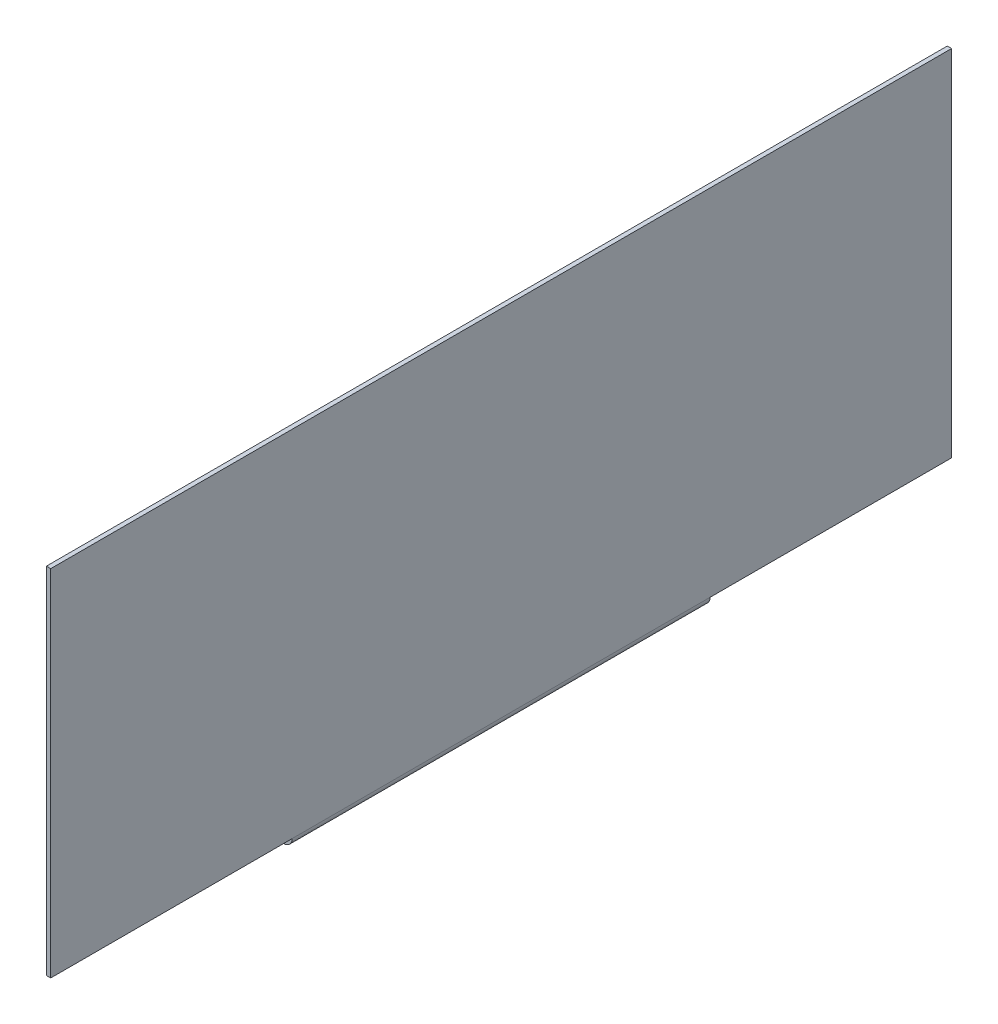
SolidWorks part; units mm, degrees
note: The reader was unsure of these and kept them because the rebuilt part matched: flange length of "Edge-Flange1".
material "6061-T6 (SS)"
ref_plane "X-Y Datum" through (0, 0, 0) normal (0, 0, 1) x (1, 0, 0)
ref_plane "X-Z Datum" through (0, 0, 0) normal (0, 1, 0) x (1, 0, 0)
ref_plane "Y-Z Datum" through (0, 0, 0) normal (1, 0, 0) x (0, 0, -1)
sketch "Sketch1" plane through (0, 0, 0) normal (1, 0, 0) x (0, 0, -1)
  line L1 (-330.7931, 130.175) -> (330.7931, 130.175)
  line L2 (-330.7931, 130.175) -> (-330.7931, -130.175)
  line L3 (-330.7931, -130.175) -> (330.7931, -130.175)
  line L4 (330.7931, 130.175) -> (330.7931, -130.175)
  line L5 (-330.7931, 130.175) -> (330.7931, -130.175) construction
  line L6 (-330.7931, -130.175) -> (330.7931, 130.175) construction
  point P0 (0, 0)
  dimension "D1" = 661.5862
  dimension "D2" = 260.35
base flange "Base-Flange1" sketch "Sketch1" thickness 3.175 reverse thickness direction no parameters "D1"=1
edge flange "Edge-Flange1" sketch "Sketch4" flange angle 90 flange length 25.4 flange position bend outside bend radius 3.175 thickness 3.175 relief rectangular parameters "D6"=10
sketch "Sketch4" plane through (-3.175, -130.175, 0) normal (0, 1, 0) x (0, 0, -1)
  line L3 (-153.4389, 22.225) -> (153.4389, 22.225)
  line L5 (330.7931, 0) -> (-330.7931, 0) construction
  line L6 (153.4389, 0) -> (-153.4389, 0)
  line L8 (-153.4389, 22.225) -> (-153.4389, 0)
  line L10 (153.4389, 22.225) -> (153.4389, 0)
bend "EdgeBend1" bend radius 3.175 bend angle 90 parameters "D5"=1
sketch "Bend-Lines1" [suppressed] plane through (0, 0, 0) normal (0, 1, 0) x (1, 0, 0)
sketch "Bounding-Box1" [suppressed] plane through (0, 0, 0) normal (0, 1, 0) x (1, 0, 0)
sheet metal parameters "Sheet-Metal1" thickness 3.175 parameters "D1"=1
flat pattern "Flat-Pattern1" [suppressed]
sketch "Bend-Lines2" plane through (0, 0, 0) normal (0, 1, 0) x (1, 0, 0)
sketch3d "Bounding-Box2" [suppressed]
  line L0 (-312.7426, -107.4737, 0) -> (312.7426, -107.4737, 0) construction
  line L1 (-312.7426, 107.4738, 0) -> (312.7426, 107.4738, 0) construction
  line L2 (-312.7426, -107.4737, 0) -> (-312.7426, 107.4738, 0) construction
  line L3 (312.7426, -107.4737, 0) -> (312.7426, 107.4738, 0) construction
sheet metal parameters "Sheet-Metal4" thickness 3.175 parameters "D1"=1
flat pattern "Flat-Pattern1"
sketch "Bend-Lines2" plane through (0, 0, 0) normal (1, 0, 0) x (0, 0, -1)
  line L0 (-153.4389, -133.9155) -> (153.4389, -133.9155) construction
  line L1 (-153.4389, -133.9155) -> (153.4389, -133.9155) construction
sketch3d "Bounding-Box2" [suppressed]
  line L0 (-330.7931, -156.7059, 0) -> (330.7931, -156.7059, 0) construction
  line L1 (-330.7931, 130.175, 0) -> (330.7931, 130.175, 0) construction
  line L2 (-330.7931, -156.7059, 0) -> (-330.7931, 130.175, 0) construction
  line L3 (330.7931, -156.7059, 0) -> (330.7931, 130.175, 0) construction
bend of the flat pattern "Flatten-<EdgeBend1>1"
